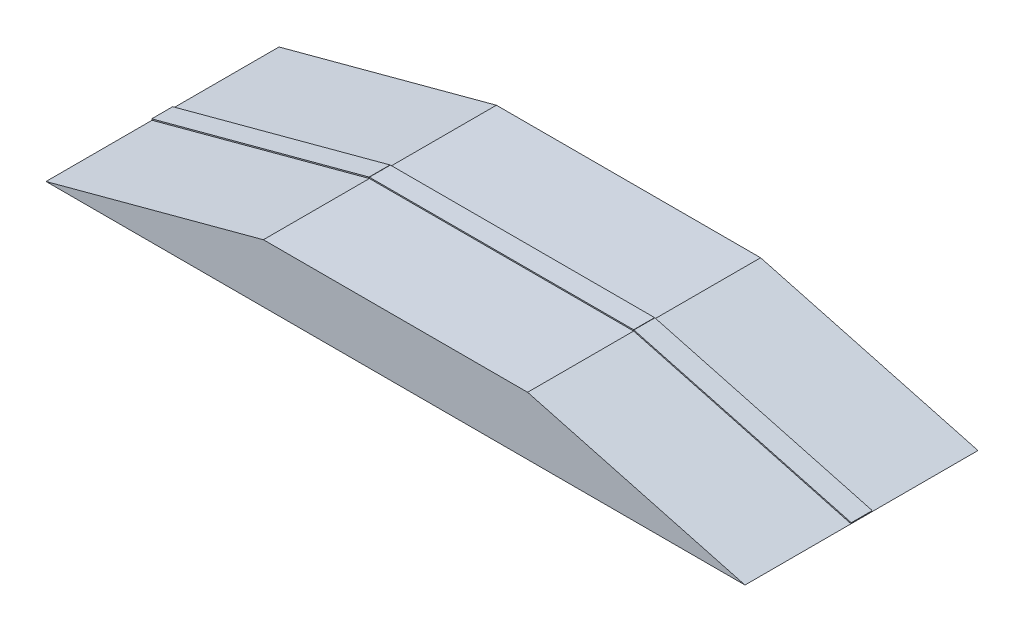
SolidWorks part; units mm, degrees
ref_plane "Front" through (0, 0, 0) normal (0, 0, 1) x (1, 0, 0)
ref_plane "Top" through (0, 0, 0) normal (0, 1, 0) x (1, 0, 0)
ref_plane "Right" through (0, 0, 0) normal (1, 0, 0) x (0, 0, -1)
sketch "草圖1" plane through (0, 0, 0) normal (0, 0, 1) x (1, 0, 0)
  line L0 (0, 0) -> (600, 0)
  line L1 (600, 0) -> (413.3975, 50)
  line L2 (413.3975, 50) -> (186.6025, 50)
  line L3 (186.6025, 50) -> (0, 0)
  dimension "D1" = 600
  dimension "D2" = 50
  dimension "D3" = 15
  dimension "D4" = 15
  dimension "D5" = 226.7949
extrude "填料-伸長1" add sketch "草圖1" along normal mid plane 200
sketch "草圖3" plane through (40.1924, 150, 0) normal (0.2588, 0.9659, 0) x (0.9659, -0.2588, 0)
  line L0 (579.5555, -100) -> (579.5555, 100) construction
  line L1 (579.5555, 9) -> (386.3703, 9)
  line L2 (579.5555, 9) -> (579.5555, -9)
  line L3 (579.5555, -9) -> (386.3703, -9)
  line L4 (386.3703, 9) -> (386.3703, -9)
  line L5 (386.3703, -100) -> (386.3703, 100) construction
  line L6 (579.5555, -100) -> (386.3703, -100) construction
  dimension "D1" = 18
  dimension "D2" = 91
extrude "填料-伸長2" add sketch "草圖3" along normal blind 1 separate body
sketch "草圖4" plane through (0, 50, 0) normal (0, 1, 0) x (1, 0, 0)
  line L0 (186.6025, -100) -> (186.6025, 100) construction
  line L1 (413.3975, 9) -> (186.6025, 9)
  line L2 (413.3975, 9) -> (413.3975, -9)
  line L3 (413.3975, -9) -> (186.6025, -9)
  line L4 (186.6025, 9) -> (186.6025, -9)
extrude "填料-伸長3" add sketch "草圖4" along normal blind 1 separate body
sketch "草圖5" plane through (0, 0, 0) normal (-0.2588, 0.9659, 0) x (0.9659, 0.2588, 0)
  line L0 (0, -100) -> (0, 100) construction
  line L1 (193.1852, 9) -> (0, 9)
  line L2 (193.1852, 9) -> (193.1852, -9)
  line L3 (193.1852, -9) -> (0, -9)
  line L4 (0, 9) -> (0, -9)
  line L5 (193.1852, 9) -> (193.1852, -9) construction
  line L6 (193.1852, -100) -> (193.1852, 100) construction
  point P7 (193.1852, -10.4361)
  dimension "D1" = 18
extrude "填料-伸長4" add sketch "草圖5" along normal blind 1 separate body
